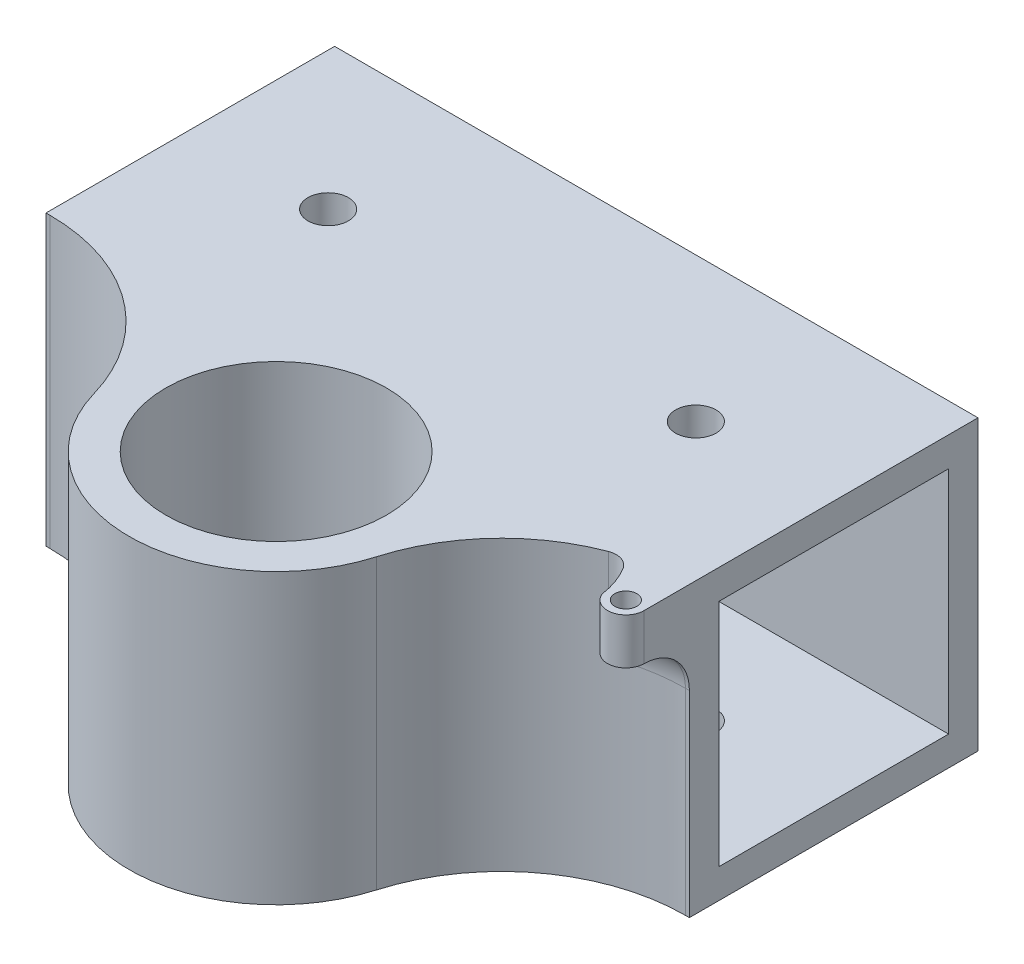
SolidWorks part; units mm, degrees
ref_plane "Front" through (0, 0, 0) normal (0, 0, 1) x (1, 0, 0)
ref_plane "Top" through (0, 0, 0) normal (0, 1, 0) x (1, 0, 0)
ref_plane "Right" through (0, 0, 0) normal (1, 0, 0) x (0, 0, -1)
sketch "Эскиз1" plane through (0, 0, 0) normal (1, 0, 0) x (0, 0, -1)
  line L1 (-12.5, -12.5) -> (12.5, -12.5)
  line L2 (-12.5, -12.5) -> (-12.5, 12.5)
  line L3 (-12.5, 12.5) -> (12.5, 12.5)
  line L4 (12.5, -12.5) -> (12.5, 12.5)
  line L5 (-12.5, -12.5) -> (12.5, 12.5) construction
  line L6 (-12.5, 12.5) -> (12.5, -12.5) construction
  point P0 (0, 0)
  dimension "D1" = 25
  dimension "D2" = 25
extrude "Вытянуть-Тонкостенный1" add sketch "Эскиз1" along normal blind 70 thin thin type one direction wall 3.2
sketch "Эскиз3" plane through (0, 15.7, 0) normal (0, 1, 0) x (1, 0, 0)
  line L0 (0, 0) -> (70, 0) construction
  line L1 (70, 15.7) -> (70, -15.7) construction
  line L2 (35, 0) -> (35, -32.0332) construction
  circle A0 centre (35, -25.6592) radius 16
  circle A1 centre (35, -25.6592) radius 6
extrude "Бобышка-Вытянуть1" add sketch "Эскиз3" against normal up to surface (31.4 mm away) up to face at (35, -15.7, 0)
sketch "Эскиз4" plane through (0, 0, 0) normal (-1, 0, 0) x (0, 0, 1)
  line L1 (12.5, -12.5) -> (-12.5, -12.5)
  line L2 (12.5, -12.5) -> (12.5, 12.5)
  line L3 (12.5, 12.5) -> (-12.5, 12.5)
  line L4 (-12.5, -12.5) -> (-12.5, 12.5)
extrude "Вырез-Вытянуть1" cut sketch "Эскиз4" against normal through all
sketch "Эскиз5" plane through (0, -15.7, 0) normal (0, -1, 0) x (1, 0, 0)
  circle A0 centre (35, 25.6592) radius 12
extrude "Вырез-Вытянуть2" cut sketch "Эскиз5" against normal blind 4
sketch "Эскиз6" plane through (0, -11.7, 0) normal (0, -1, 0) x (1, 0, 0)
  circle A0 centre (35, 25.6592) radius 8 construction
  circle A1 centre (35, 33.6592) radius 1.5
  circle A2 centre (27, 25.6592) radius 1.5
  circle A3 centre (43, 25.6592) radius 1.5
  circle A4 centre (35, 17.6592) radius 1.5
extrude "Вырез-Вытянуть3" cut sketch "Эскиз6" against normal through all
fillet "Скругление1" radius 20 2 edges at (47.5225, 0, 15.7) (22.4775, 0, 15.7)
sketch "Эскиз7" plane through (0, 15.7, 0) normal (0, 1, 0) x (1, 0, 0)
  circle A0 centre (35, -25.6592) radius 12
extrude "Вырез-Вытянуть4" cut sketch "Эскиз7" against normal blind 20
sketch "Эскиз8" plane through (0, 15.7, 0) normal (0, 1, 0) x (1, 0, 0)
  line L0 (0, 0) -> (70, 0) construction
  line L1 (70, 15.7) -> (70, -15.7) construction
  line L2 (0, 15.7) -> (0, -15.7) construction
  circle A0 centre (15, 0) radius 2.2
  circle A1 centre (55, 0) radius 2.2
  dimension "D1" = 15
  dimension "D2" = 15
extrude "Вырез-Вытянуть5" cut sketch "Эскиз8" against normal through all
sketch "Эскиз9" plane through (0, 15.7, 0) normal (0, -1, 0) x (1, 0, 0)
  line L0 (70, 15.7) -> (70, 20.6235)
  circle A0 centre (68.0094, 20.6235) radius 1.2
  arc A1 (70, 20.6235) -> (66.1427, 21.3149) centre (68.0094, 20.6235) ccw
  arc A2 (66.1427, 21.3149) -> (63.9425, 16.5085) centre (56.9875, 22.599) cw
  arc A6 (50.3651, 30.1218) -> (69.5714, 15.7) centre (69.5714, 35.7) ccw construction
  arc A7 (63.9425, 16.5085) -> (70, 15.7) centre (69.5992, 35.7949) ccw
  point P13 (66.0188, 20.6235)
extrude "Бобышка-Вытянуть4" add sketch "Эскиз9" along normal blind 5
fillet "Скругление2" radius 5 2 edges at (69.7857, 10.7, 15.7) (66.7281, 10.7, 15.9031)
fillet "Скругление3" radius 2 1 edges at (63.9425, 10.7, 16.5085)
